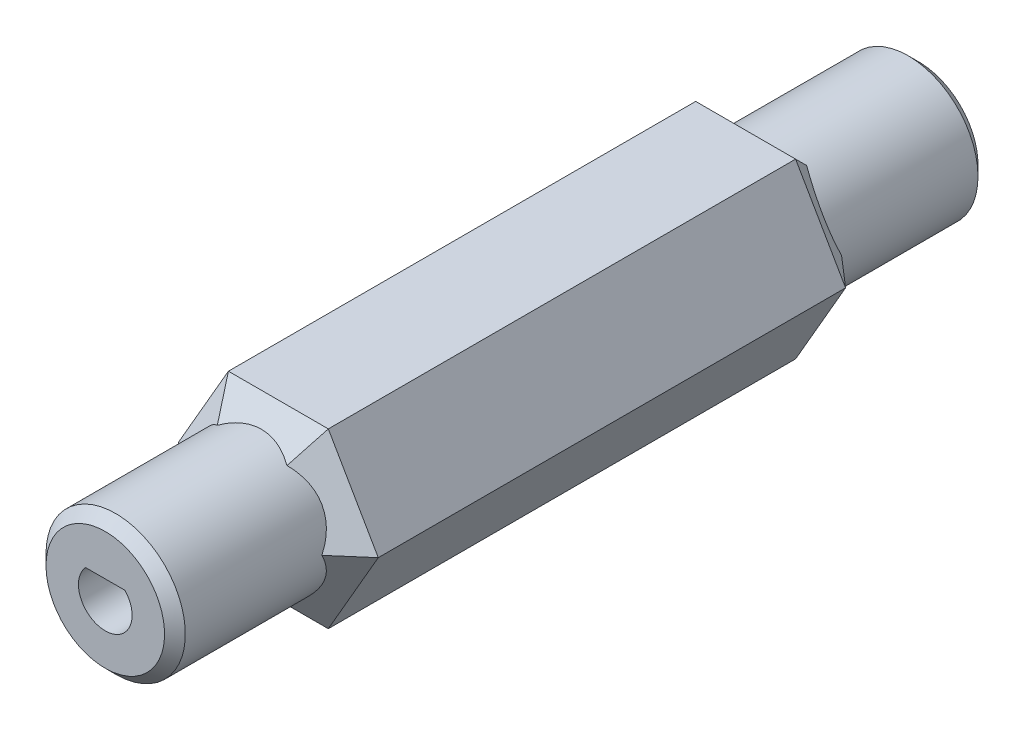
SolidWorks part; units mm, degrees
ref_plane "前视基准面" through (0, 0, 0) normal (0, 0, 1) x (1, 0, 0)
ref_plane "上视基准面" through (0, 0, 0) normal (0, 1, 0) x (1, 0, 0)
ref_plane "右视基准面" through (0, 0, 0) normal (1, 0, 0) x (0, 0, -1)
sketch "草图1" plane through (0, 0, 0) normal (0, 0, 1) x (1, 0, 0)
  line L1 (5.7735, 0) -> (2.8868, 5)
  line L2 (2.8868, 5) -> (-2.8868, 5)
  line L3 (-2.8868, 5) -> (-5.7735, 0)
  line L4 (-5.7735, 0) -> (-2.8868, -5)
  line L5 (-2.8868, -5) -> (2.8868, -5)
  line L6 (2.8868, -5) -> (5.7735, 0)
  circle A0 centre (0, 0) radius 5 construction
  dimension "D1" = 10
extrude "凸台-拉伸1" add sketch "草图1" along normal blind 30
sketch "草图2" plane through (0, 0, 30) normal (0, 0, 1) x (1, 0, 0)
  circle A0 centre (0, 0) radius 4.025
  dimension "D1" = 8.05
extrude "凸台-拉伸2" add sketch "草图2" along normal blind 8.5
chamfer "倒角1" distance 0.6 angle 45 1 edges at (4.025, 0, 38.5)
sketch "草图3" plane through (0, 0, 38.5) normal (0, 0, 1) x (1, 0, 0)
  line L0 (-1.1402, 1.05) -> (1.1402, 1.05)
  arc A0 (-1.1402, 1.05) -> (1.1402, 1.05) centre (0, 0) ccw
  dimension "D1" = 3.1
  dimension "D2" = 1.05
extrude "切除-拉伸1" cut sketch "草图3" against normal blind 8
ref_plane "基准面4" through (0, 0, 15) normal (0, 0, 1) x (1, 0, 0)
mirror "镜向1" about plane through (0, 0, 15) normal (0, 0, 1) of "凸台-拉伸2", "倒角1", "切除-拉伸1"
chamfer "倒角2" distance 1.5 angle 45 12 edges at (4.3301, 2.5, 0) (4.3301, -2.5, 0) (0, -5, 0) (-4.3301, -2.5, 0) (-4.3301, 2.5, 0) (0, 5, 0) (-4.3301, 2.5, 30) (-4.3301, -2.5, 30) (0, -5, 30) (4.3301, -2.5, 30) (4.3301, 2.5, 30) (0, 5, 30)
